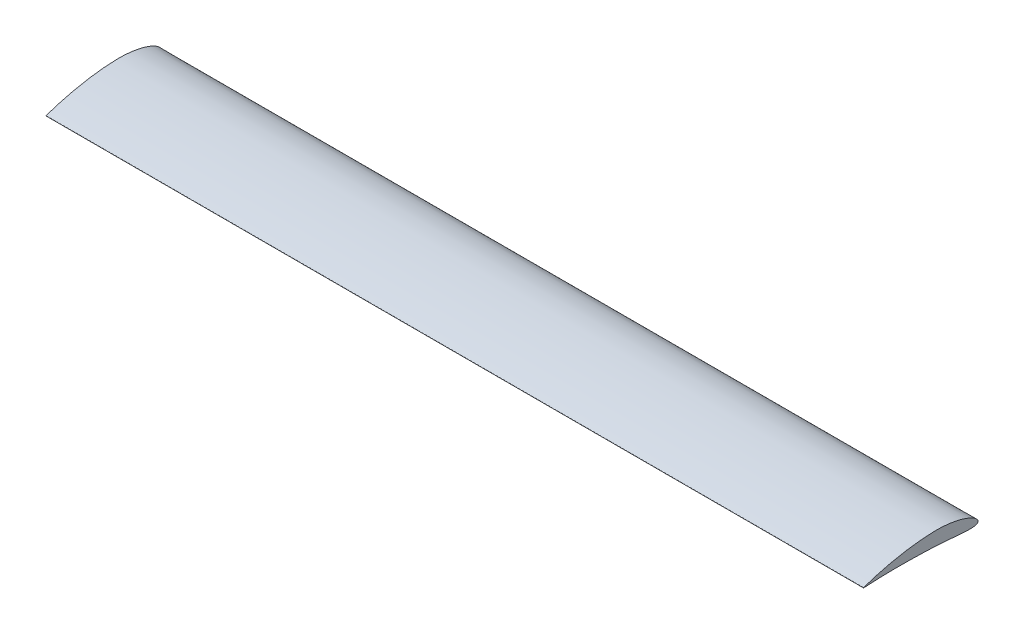
SolidWorks part; units mm, degrees
ref_plane "Front Plane" through (0, 0, 0) normal (0, 0, 1) x (1, 0, 0)
ref_plane "Top Plane" through (0, 0, 0) normal (0, 1, 0) x (1, 0, 0)
ref_plane "Right Plane" through (0, 0, 0) normal (1, 0, 0) x (0, 0, -1)
curve "Curve1"
  spline degree 3 poles (0, 0.0012, 1.0003) (0, 0.0015, 0.9994) (0, 0.0028, 0.9958) (0, 0.0055, 0.9879) (0, 0.0099, 0.9747) (0, 0.0159, 0.9565) (0, 0.0233, 0.9333) (0, 0.0318, 0.9054) (0, 0.0411, 0.8731) (0, 0.051, 0.8366) (0, 0.0612, 0.7964) (0, 0.0713, 0.7528) (0, 0.0811, 0.7063) (0, 0.0903, 0.6574) (0, 0.0985, 0.6067) (0, 0.1057, 0.5546) (0, 0.1115, 0.5018) (0, 0.1158, 0.4488) (0, 0.1186, 0.3959) (0, 0.1189, 0.3436) (0, 0.1164, 0.2927) (0, 0.1112, 0.2442) (0, 0.1037, 0.1988) (0, 0.0942, 0.157) (0, 0.0831, 0.1194) (0, 0.0711, 0.0865) (0, 0.0584, 0.0585) (0, 0.0457, 0.0357) (0, 0.0334, 0.0184) (0, 0.0218, 0.0064) (0, 0.0108, -0.0005) (0, -0.0003, -0.0011) (0, -0.0092, 0.0055) (0, -0.0148, 0.017) (0, -0.0185, 0.0329) (0, -0.0204, 0.0533) (0, -0.0208, 0.0781) (0, -0.0198, 0.107) (0, -0.0176, 0.1398) (0, -0.0147, 0.176) (0, -0.0111, 0.2153) (0, -0.0074, 0.2574) (0, -0.0037, 0.3019) (0, -0.0005, 0.3484) (0, 0.002, 0.397) (0, 0.0037, 0.4471) (0, 0.0055, 0.4983) (0, 0.0069, 0.5496) (0, 0.0079, 0.6006) (0, 0.0085, 0.6505) (0, 0.0086, 0.699) (0, 0.0083, 0.7455) (0, 0.0076, 0.7894) (0, 0.0065, 0.8302) (0, 0.0053, 0.8675) (0, 0.0039, 0.9007) (0, 0.0027, 0.9296) (0, 0.0013, 0.9539) (0, 0.0006, 0.9727) (0, -0.0011, 0.9872) (0, 0, 0.9944) (0, -0.002, 0.9999) (0, -0.0005, 1) (0, 0, 1) knots 0 0 0 0 0.001372 0.005465 0.012235 0.021602 0.033461 0.047671 0.064081 0.082496 0.102719 0.124527 0.147676 0.171913 0.196978 0.222597 0.248497 0.274385 0.300041 0.32569 0.350525 0.37428 0.396711 0.417577 0.436654 0.453744 0.46868 0.481329 0.491631 0.499616 0.505546 0.510185 0.514824 0.520702 0.528516 0.538466 0.550543 0.564643 0.580638 0.598345 0.617584 0.638174 0.659922 0.682632 0.706121 0.730727 0.7557 0.780732 0.805564 0.829932 0.85357 0.876213 0.89761 0.917519 0.935698 0.951943 0.966047 0.97784 0.987174 0.993932 0.998018 0.999386 1 1 1 1
sketch "Sketch1" plane through (0, 0, 0) normal (1, 0, 0) x (0, 0, -1)
  line L0 (-354.7873, -0.0303) -> (-354.8762, 0.4104)
  line L1 (-354.7873, -0.0303) -> (0.8093, 1.5275) construction
  line L2 (0.8093, 1.5275) -> (0.7921, 5.4415) construction
  spline S1 degree 3 poles (-354.8762, 0.4104) (-354.5599, 0.5194) (-353.2997, 0.9536) (-350.4787, 1.9271) (-345.801, 3.4978) (-336.0241, 6.7216) (-319.6545, 11.7989) (-300.5983, 17.1306) (-282.4229, 21.7243) (-261.1758, 26.6516) (-238.6223, 31.1455) (-208.7748, 36.0048) (-183.9617, 39.0905) (-158.9023, 41.1132) (-140.0967, 42.1114) (-121.5167, 42.2289) (-103.4222, 41.3211) (-86.1884, 39.4787) (-70.0435, 36.8105) (-55.1998, 33.4329) (-41.8434, 29.5109) (-30.1305, 25.2201) (-20.187, 20.7343) (-12.1072, 16.2263) (-5.9269, 11.8553) (-1.6792, 7.7165) (0.7658, 3.7968) (0.9875, -0.1483) (-1.3511, -3.3089) (-5.4508, -5.2881) (-11.0873, -6.5875) (-18.3491, -7.2685) (-27.1638, -7.4049) (-37.4471, -7.0538) (-49.0831, -6.3019) (-61.9524, -5.238) (-75.9299, -3.9839) (-96.4067, -2.1536) (-117.9372, -0.4584) (-140.4848, 0.6745) (-158.2965, 1.2867) (-176.4839, 1.9179) (-200.672, 2.5862) (-224.5411, 2.9791) (-247.8302, 3.0285) (-264.3373, 2.9074) (-279.9331, 2.6564) (-294.438, 2.2829) (-307.6819, 1.8521) (-319.5134, 1.3711) (-329.7674, 0.9129) (-338.3889, 0.4268) (-345.077, 0.1915) (-350.2276, -0.4064) (-352.7802, -0.0354) (-354.7446, -0.7581) (-354.7772, -0.2025) (-354.7873, -0.0303) knots 0 0 0 0 0.001372 0.005465 0.012235 0.021602 0.047671 0.082496 0.102719 0.124527 0.171913 0.196978 0.248497 0.274385 0.300041 0.32569 0.350525 0.37428 0.396711 0.417577 0.436654 0.453744 0.46868 0.481329 0.491631 0.499616 0.505546 0.510185 0.514824 0.520702 0.528516 0.538466 0.550543 0.564643 0.580638 0.598345 0.617584 0.638174 0.682632 0.706121 0.730727 0.7557 0.780732 0.829932 0.85357 0.876213 0.89761 0.917519 0.935698 0.951943 0.966047 0.97784 0.987174 0.993932 0.998018 0.999386 1 1 1 1
  dimension "D1" = 355.6
extrude "Boss-Extrude1" add sketch "Sketch1" along normal blind 1270 and the other way blind 1270
